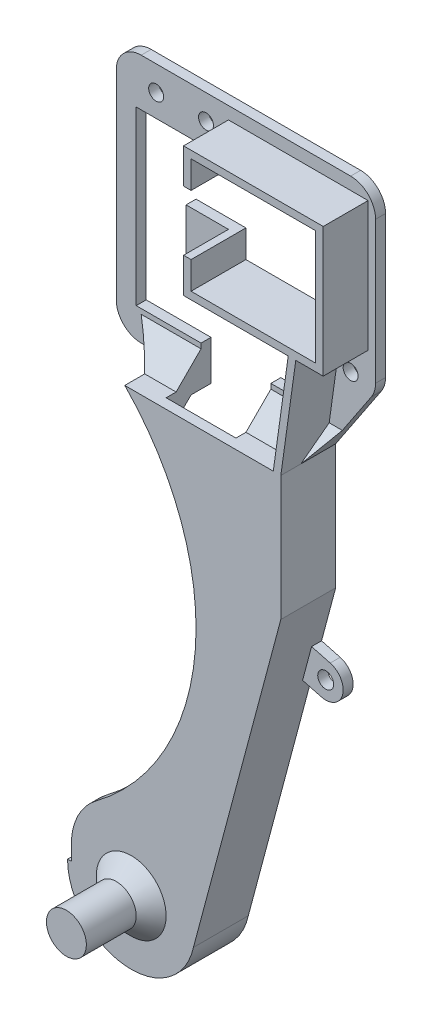
SolidWorks part; units mm, degrees
ref_plane "前视基准面" through (0, 0, 0) normal (0, 0, 1) x (1, 0, 0)
ref_plane "上视基准面" through (0, 0, 0) normal (0, 1, 0) x (1, 0, 0)
ref_plane "右视基准面" through (0, 0, 0) normal (1, 0, 0) x (0, 0, -1)
sketch "草图1" plane through (0, 0, 0) normal (1, 0, 0) x (0, 0, -1)
  line L0 (0, 0) -> (0, 98)
  line L1 (0, 98) -> (9, 98)
  line L2 (9, 98) -> (9, 150)
  line L3 (7, 150) -> (7, 100)
  line L4 (7, 100) -> (-2, 100)
  line L5 (-2, 100) -> (-2, 0)
  line L6 (-2, 0) -> (0, 0)
  line L7 (7, 150) -> (9, 150)
  point P9 (2.5, 100)
  dimension "D1" = 2
  dimension "D2" = 2
  dimension "D3" = 2
  dimension "D4" = 9
  dimension "D5" = 52
  dimension "D6" = 100
extrude "凸台-拉伸1" add sketch "草图1" along normal blind 52
sketch "草图2" plane through (0, 0, -7) normal (0, 0, 1) x (1, 0, 0)
  line L9 (52, 98) -> (0, 98) construction
  line L18 (24, 146) -> (49, 146)
  line L19 (24, 140.5) -> (24, 146)
  line L20 (4, 140.5) -> (24, 140.5)
  line L22 (4, 106) -> (4, 140.5)
  line L23 (17, 106) -> (4, 106)
  line L24 (17, 98) -> (17, 106)
  line L25 (31, 98) -> (17, 98)
  line L26 (31, 106) -> (31, 98)
  line L27 (41, 106) -> (31, 106)
  line L28 (41, 117) -> (41, 106)
  line L29 (14, 117) -> (41, 117)
  line L30 (14, 128.5) -> (14, 117)
  line L31 (24, 128.5) -> (14, 128.5)
  line L32 (24, 123) -> (24, 128.5)
  line L33 (49, 123) -> (24, 123)
  line L34 (49, 146) -> (49, 123)
  line L35 (52, 98) -> (52, 150) construction
  dimension "D1" = 23
  dimension "D2" = 12
  dimension "D3" = 5.5
  dimension "D4" = 10
  dimension "D5" = 6
  dimension "D6" = 17
  dimension "D7" = 25
  dimension "D8" = 25
  dimension "D9" = 8
  dimension "D10" = 20
  dimension "D11" = 10
  dimension "D12" = 10
  dimension "D13" = 3
  dimension "D14" = 14
extrude "切除-拉伸1" cut sketch "草图2" against normal up to next and the other way blind 7
sketch "草图3" plane through (0, 0, 2) normal (0, 0, 1) x (1, 0, 0)
  line L1 (16.7806, 145) -> (-11.2662, 145) construction
  line L2 (52, 150) -> (0, 150) construction
  line L5 (0, 0) -> (0, 100) construction
  line L6 (52, 0) -> (0, 0) construction
  line L7 (0, 100) -> (10.7071, 100)
  line L9 (0, 0) -> (0, 98) construction
  line L10 (42, 75) -> (42, 100)
  line L11 (52, 100) -> (0, 100) construction
  line L13 (0, 150) -> (0, 100) construction
  line L14 (0, 100) -> (0, 21.6987)
  line L16 (42, 100) -> (52, 115)
  line L18 (52, 100) -> (0, 100) construction
  line L19 (52, 100) -> (31, 100) construction
  line L22 (42, 75) -> (22, 0)
  line L25 (52, 98) -> (52, 150) construction
  line L26 (52, 115) -> (52, 0)
  line L27 (52, 0) -> (22, 0)
  arc A17 (10.7071, 100) -> (0, 21.6987) centre (-25, 65) cw
  circle A19 centre (8, 145) radius 1.5
  circle A20 centre (18, 145) radius 1.5
  circle A21 centre (47, 116) radius 1.5
  point P29 (41.5005, 100)
  dimension "D4" = 3
  dimension "D5" = 10
  dimension "D6" = 22
  dimension "D8" = 25
  dimension "D9" = 3
  dimension "D10" = 5
  dimension "D11" = 8
  dimension "D12" = 16
  dimension "D13" = 15
  dimension "D1" = 50
  dimension "D2" = 3
  dimension "D14" = 5
  dimension "D3" = 65
  dimension "D7" = 25
  dimension "D15" = 10
extrude "切除-拉伸2" cut sketch "草图3" against normal through all
sketch "草图5" plane through (0, 0, 0) normal (0, 0, -1) x (-1, 0, 0)
  line L0 (-22, 0) -> (0, 0) construction
  line L1 (0, 21.6987) -> (0, 0) construction
  circle A0 centre (-12, 12) radius 4
  dimension "D1" = 8
  dimension "D3" = 12
  dimension "D2" = 12
extrude "凸台-拉伸3" add sketch "草图5" against normal blind 15
fillet "圆角1" radius 5 4 edges at (52, 150, -8) (0, 150, -8) (52, 115, -8) (0, 100, -8)
chamfer "倒角1" distance 5 angle 45 2 edges at (13.8536, 100, -7) (36.5, 100, -7)
fillet "圆角2" radius 12.5 3 edges at (0, 0, 1) (22, 0, 1) (0, 21.6987, 1)
sketch "草图4" plane through (0, 0, -7) normal (0, 0, 1) x (1, 0, 0)
  line L20 (24, 128.5) -> (24, 123)
  line L21 (24, 123) -> (49, 123)
  line L22 (49, 123) -> (49, 146)
  line L23 (49, 146) -> (24, 146)
  line L24 (24, 146) -> (24, 140.5)
  line L25 (24, 140.5) -> (22.5, 140.5)
  line L26 (24, 140.5) -> (4, 140.5) construction
  line L27 (22.5, 140.5) -> (22.5, 147.5)
  line L28 (22.5, 147.5) -> (50.5, 147.5)
  line L29 (50.5, 147.5) -> (50.5, 121.5)
  line L30 (50.5, 121.5) -> (45, 121.5)
  line L31 (22.5, 121.5) -> (22.5, 128.5)
  line L32 (14, 128.5) -> (24, 128.5) construction
  line L33 (22.5, 128.5) -> (24, 128.5)
  line L34 (40.4855, 100) -> (42, 100)
  line L35 (42, 100) -> (31, 100) construction
  line L36 (42, 100) -> (45, 121.5)
  line L38 (43.4855, 121.5) -> (40.4855, 100)
  line L39 (43.4855, 121.5) -> (22.5, 121.5)
  point P55 (42, 100)
  dimension "D7" = 1.5
  dimension "D8" = 1.5
  dimension "D9" = 1.5
  dimension "D10" = 1.5
  dimension "D11" = 1.5
  dimension "D12" = 5.5
extrude "凸台-拉伸2" add sketch "草图4" along normal blind 9
chamfer "倒角2" distance 5 angle 45 2 edges at (14.7816, 98, 0) (36.5, 98, 0)
sketch "草图6" plane through (0, 0, 0) normal (0, 0, -1) x (-1, 0, 0)
  line L0 (-40.5, 100) -> (-42, 100)
  line L1 (-42, 100) -> (-42, 75)
  line L2 (-42, 75) -> (-24.4745, 9.2792)
  line L4 (-23.0392, 9.7185) -> (-40.5, 75.1966)
  line L5 (-40.5, 75.1966) -> (-40.5, 100)
  line L6 (-0.7275, 12) -> (0.7677, 12)
  arc A0 (-24.4745, 9.2792) -> (0.7677, 12) centre (-12, 12) ccw
  arc A1 (-23.0392, 9.7185) -> (-0.7275, 12) centre (-12, 12) ccw
  dimension "D1" = 1.5
  dimension "D2" = 1.5
extrude "凸台-拉伸4" add sketch "草图6" along normal blind 9 and the other way blind 2
chamfer "倒角3" distance 3 angle 45 1 edges at (12, 16, 2)
sketch "草图7" plane through (0, 0, -9) normal (0, 0, -1) x (-1, 0, 0)
  line L0 (-39.1674, 64.3777) -> (-42.9018, 63.3818)
  line L1 (-42, 75) -> (-24.4745, 9.2792) construction
  line L2 (-41.0982, 56.6182) -> (-37.3637, 57.614)
  line L3 (-39.1674, 64.3777) -> (-37.3637, 57.614)
  arc A0 (-42.9018, 63.3818) -> (-41.0982, 56.6182) centre (-42, 60) ccw
  circle A1 centre (-42, 60) radius 1.6
  dimension "D1" = 7
  dimension "D2" = 3.2
  dimension "D3" = 42
  dimension "D4" = 60
extrude "凸台-拉伸5" add sketch "草图7" against normal blind 2
